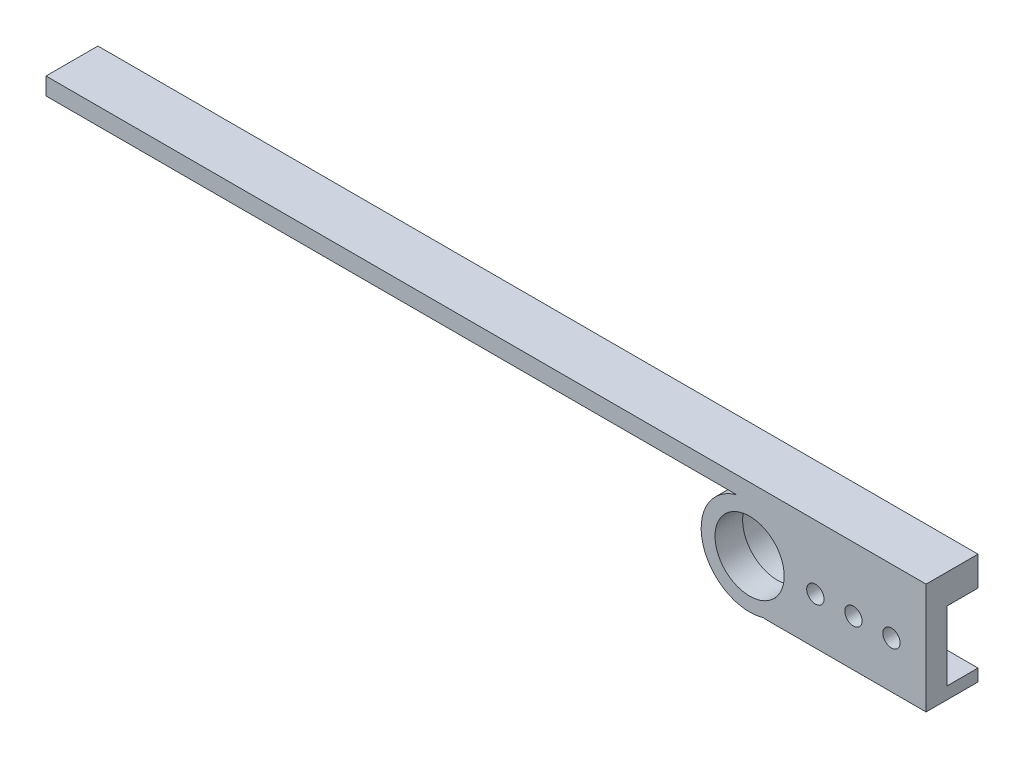
SolidWorks part; units mm, degrees
ref_plane "前视基准面" through (0, 0, 0) normal (0, 0, 1) x (1, 0, 0)
ref_plane "上视基准面" through (0, 0, 0) normal (0, 1, 0) x (1, 0, 0)
ref_plane "右视基准面" through (0, 0, 0) normal (1, 0, 0) x (0, 0, -1)
sketch "草图1" plane through (0, 0, 0) normal (0, 0, 1) x (1, 0, 0)
  line L1 (20, -10) -> (-20, -10)
  line L2 (20, -10) -> (20, 10)
  line L3 (20, 10) -> (-20, 10)
  line L4 (-20, -10) -> (-20, 10)
  line L5 (20, -10) -> (-20, 10) construction
  line L6 (20, 10) -> (-20, -10) construction
  point P0 (0, 0)
  dimension "D1" = 40
  dimension "D2" = 20
extrude "凸台-拉伸1" add sketch "草图1" along normal blind 6
sketch "草图2" plane through (0, 0, 6) normal (0, 0, 1) x (1, 0, 0)
  line L0 (20, -10) -> (20, 10) construction
  circle A0 centre (10, 0) radius 2.5
  circle A1 centre (-1, 0) radius 2.5
  circle A2 centre (-12, 0) radius 2.5
  dimension "D1" = 10
  dimension "D2" = 5
  dimension "D3" = 3
extrude "切除-拉伸1" cut sketch "草图2" against normal through all
sketch "草图3" plane through (0, 0, 6) normal (0, 0, 1) x (1, 0, 0)
  line L0 (20, 13.5) -> (20, 10)
  line L1 (20, -13.5) -> (-26.894, -13.5)
  line L3 (20, 13.5) -> (-26.894, 13.5)
  line L4 (-20, 10) -> (-20, -10)
  line L5 (-20, -10) -> (20, -10)
  line L6 (20, -10) -> (20, 10)
  line L7 (20, 10) -> (-20, 10)
  line L8 (-20, 10) -> (-20, -10)
  line L9 (-20, -10) -> (20, -10)
  line L10 (20, -10) -> (20, 10)
  line L11 (20, 10) -> (-20, 10)
  line L12 (-26.894, -13.5) -> (-26.894, 13.5)
  line L13 (20, -10.0394) -> (-26.894, 13.5) construction
  line L14 (20, 10.0394) -> (-26.894, -13.5) construction
  line L15 (20, -10) -> (20, -13.5)
  circle A0 centre (-31, 0) radius 11
  circle A1 centre (-31, 0) radius 14
  point P2 (0, 0)
  line M10 (-20, 10) -> (-20, -10)
  line M11 (-20, -10) -> (20, -10)
  line M13 (20, 10) -> (-20, 10)
  dimension "D3" = 22
  dimension "D4" = 28
  dimension "D2" = 3.5
  dimension "D1" = 0
extrude "凸台-拉伸2" add sketch "草图3" against normal blind 15 contours L3 A1 L1 L12 A0 | A1 L1 L15 M11 M10 | L1 A1 L8 A0 L12 | L8 A1 L3 L12 A0 | L8 A1 | A1 L0 L3 M10 M13 region at (-1.9449, 11.7771, 6) region at (-1.9449, -11.7771, 6) region at (-23.0173, 9.0328, 6) region at (-27.2274, 11.7946, 6) region at (-18.7882, 0, 6) region at (-23.0173, -9.0328, 6)
sketch "草图5" plane through (0, 0, 6) normal (0, 0, 1) x (1, 0, 0)
  circle A0 centre (-31, 0) radius 10
  circle A1 centre (-31, 0) radius 11 construction
  circle A2 centre (-31, 0) radius 11
  dimension "D1" = 20
extrude "凸台-拉伸3" add sketch "草图5" against normal blind 8
sketch "草图6" plane through (0, 0, 6) normal (0, 0, 1) x (1, 0, 0)
  circle A0 centre (-31, 0) radius 8.5
  circle A1 centre (-31, 0) radius 10 construction
  circle A2 centre (-31, 0) radius 10
  dimension "D1" = 17
sketch "草图7" plane through (0, 13.5, 0) normal (0, 1, 0) x (1, 0, 0)
  circle A0 centre (-17.1666, 1.953) radius 2.6594
sketch "草图8" plane through (20, 0, 0) normal (1, 0, 0) x (0, 0, -1)
  line L1 (-6, 13.5) -> (9, 13.5)
  line L2 (-6, 13.5) -> (-6, 18.5)
  line L3 (-6, 18.5) -> (9, 18.5)
  line L4 (9, 13.5) -> (9, 18.5)
  dimension "D1" = 5
extrude "凸台-拉伸4" add sketch "草图8" against normal blind 500
sketch "草图9" plane through (0, 0, -9) normal (0, 0, -1) x (-1, 0, 0)
  line L1 (24.4567, 15.8334) -> (28.494, 15.8334)
  line L2 (24.4567, 15.8334) -> (24.4567, 12.469)
  line L3 (24.4567, 12.469) -> (28.494, 12.469)
  line L4 (28.494, 15.8334) -> (28.494, 12.469)
extrude "凸台-拉伸5" add sketch "草图9" against normal through all
sketch "草图10" plane through (0, 18.5, 0) normal (0, 1, 0) x (1, 0, 0)
  line L0 (-234.3163, -8.9161) -> (-234.3163, 9)
  line L1 (-234.3163, -8.9161) -> (-95.8824, -8.9161) construction
  line L2 (-234.3163, 238.5858) -> (-234.3163, -131.4142) construction
  line L3 (-480, 9) -> (20, 9) construction
sketch "草图11" plane through (0, 18.5, 0) normal (0, 1, 0) x (1, 0, 0)
  line L1 (-234.3163, -8.9161) -> (-495.6366, -8.9161)
  line L2 (-234.3163, -8.9161) -> (-234.3163, 25.3653)
  line L3 (-234.3163, 25.3653) -> (-495.6366, 25.3653)
  line L4 (-495.6366, -8.9161) -> (-495.6366, 25.3653)
extrude "切除-拉伸2" cut sketch "草图11" against normal through all
